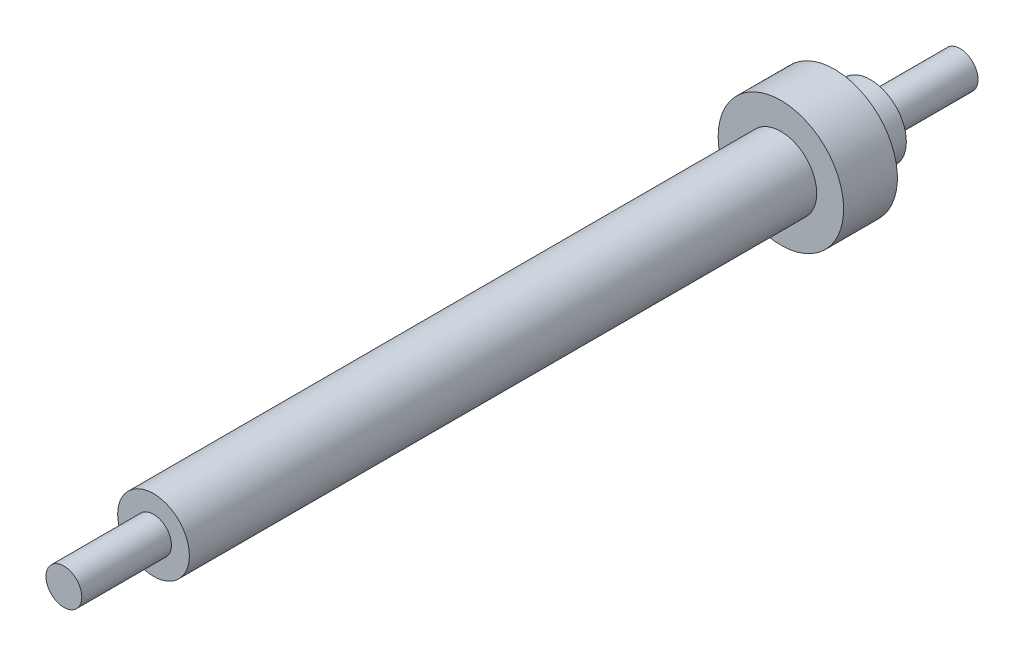
SolidWorks part; units mm, degrees
material "Сталь ШХ15 ГОСТ 801-78"
ref_plane "Plane1" through (0, 0, 0) normal (0, 0, 1) x (1, 0, 0)
ref_plane "Plane2" through (0, 0, 0) normal (0, 1, 0) x (1, 0, 0)
ref_plane "Plane3" through (0, 0, 0) normal (1, 0, 0) x (0, 0, -1)
sketch "Эскиз1" plane through (0, 0, 0) normal (0, 0, 1) x (1, 0, 0)
  circle A0 centre (0, 0) radius 2
  dimension "D1" = 4
extrude "Бобышка-Вытянуть1" add sketch "Эскиз1" along normal blind 40 contours A0
sketch "Эскиз2" plane through (0, 0, 40) normal (0, 0, 1) x (1, 0, 0)
  circle A0 centre (0, 0) radius 1
  dimension "D1" = 2
extrude "Бобышка-Вытянуть2" add sketch "Эскиз2" along normal blind 5 contours A0
sketch "Эскиз4" plane through (0, 0, 0) normal (0, 0, -1) x (-1, 0, 0)
  circle A0 centre (0, 0) radius 1
  dimension "D1" = 2
extrude "Бобышка-Вытянуть3" add sketch "Эскиз4" along normal blind 5
sketch "Эскиз6" plane through (0, 0, 0) normal (0, 0, -1) x (-1, 0, 0)
  circle A0 centre (0, 0) radius 3.5
  dimension "D1" = 7
extrude "Бобышка-Вытянуть5" add sketch "Эскиз6" along normal blind 3 from offset 5 offset against normal yes
